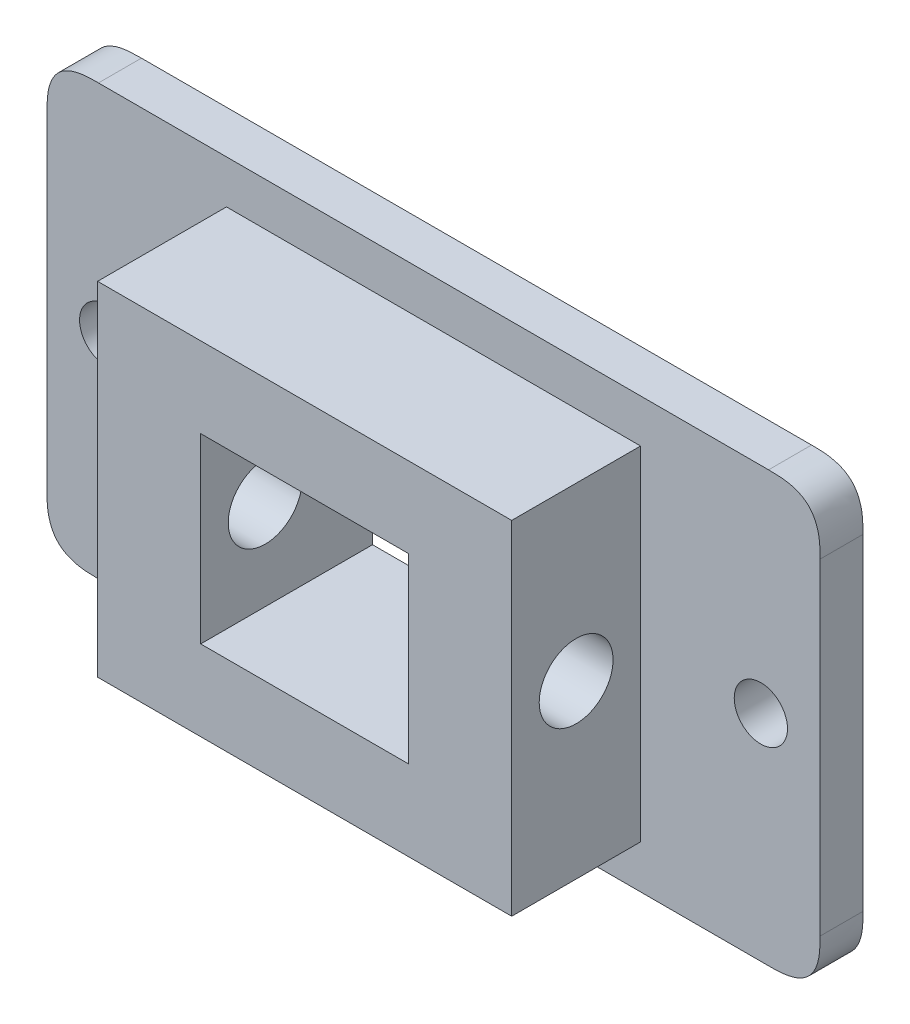
SolidWorks part; units mm, degrees
ref_plane "Front Plane" through (0, 0, 0) normal (0, 0, 1) x (1, 0, 0)
ref_plane "Top Plane" through (0, 0, 0) normal (0, 1, 0) x (1, 0, 0)
ref_plane "Right Plane" through (0, 0, 0) normal (1, 0, 0) x (0, 0, -1)
sketch "Sketch1" plane through (0, 0, 0) normal (0, 0, 1) x (1, 0, 0)
  line L1 (-6.05, 5.3) -> (6.05, 5.3)
  line L2 (-6.05, 5.3) -> (-6.05, -5.3)
  line L3 (-6.05, -5.3) -> (6.05, -5.3)
  line L4 (6.05, 5.3) -> (6.05, -5.3)
  line L5 (-6.05, 5.3) -> (6.05, -5.3) construction
  line L6 (-6.05, -5.3) -> (6.05, 5.3) construction
  line L7 (-22.5, 12.5) -> (22.5, 12.5)
  line L8 (-22.5, 12.5) -> (-22.5, -12.5)
  line L9 (-22.5, -12.5) -> (22.5, -12.5)
  line L10 (22.5, 12.5) -> (22.5, -12.5)
  line L11 (-22.5, 12.5) -> (22.5, -12.5) construction
  line L12 (-22.5, -12.5) -> (22.5, 12.5) construction
  point P0 (0, 0)
  point P5 (0, 0)
  dimension "D1" = 10.6
  dimension "D2" = 12.1
  dimension "D3" = 25
  dimension "D4" = 45
extrude "Boss-Extrude1" add sketch "Sketch1" along normal blind 2.5
sketch "Sketch2" plane through (0, 0, 2.5) normal (0, 0, 1) x (1, 0, 0)
  line L1 (-6.05, -5.3) -> (6.05, -5.3)
  line L2 (-6.05, -5.3) -> (-6.05, -12.5)
  line L3 (-6.05, -12.5) -> (6.05, -12.5)
  line L4 (6.05, -5.3) -> (6.05, -12.5)
  line L5 (-22.5, -12.5) -> (22.5, -12.5) construction
  line L6 (22.5, 12.5) -> (-22.5, 12.5) construction
  line L7 (6.05, 5.3) -> (-6.05, 5.3)
  line L8 (6.05, 5.3) -> (6.05, 12.5)
  line L9 (6.05, 12.5) -> (-6.05, 12.5)
  line L10 (-6.05, 5.3) -> (-6.05, 12.5)
  dimension "D1" = 7.2
  dimension "D2" = 12.1
  dimension "D3" = 12.1
extrude "Boss-Extrude2" add sketch "Sketch2" along normal blind 7.5
sketch "Sketch3" plane through (0, 0, 0) normal (1, 0, 0) x (0, 0, -1)
  line L0 (0, -5.3) -> (-10, -5.3) construction
  line L1 (-10, -5.3) -> (-2.5, -5.3) construction
  line L2 (-10, -5.3) -> (-10, 5.3) construction
  line L3 (-2.5, -5.3) -> (-10, -5.3) construction
  line L4 (-2.5, -12.5) -> (-2.5, 12.5) construction
  line L6 (-2.5, 12.5) -> (-10, 12.5)
  line L7 (-2.5, 12.5) -> (-2.5, -12.5)
  line L8 (-2.5, -12.5) -> (-10, -12.5)
  line L9 (-10, 12.5) -> (-10, -12.5)
  circle A0 centre (-6.25, 0) radius 2.15
  point P12 (-6.25, -5.3)
  dimension "D3" = 4.3
  dimension "D1" = 10
  dimension "D2" = 10.6
extrude "Boss-Extrude3" add sketch "Sketch3" along normal blind 6 from surface starting at face at (6.05, -8.9, 6.25)
extrude "Boss-Extrude4" add sketch "Sketch3<2>" against normal blind 8 from surface starting at face at (-6.05, -8.9, 6.25)
sketch "Sketch3<2>" plane through (0, 0, 0) normal (1, 0, 0) x (0, 0, -1) same geometry as "Sketch3"
sketch "Sketch5" plane through (0, 0, 0) normal (0, 0, -1) x (-1, 0, 0)
  line L0 (-22.5, -12.5) -> (-22.5, 12.5) construction
  line L1 (22.5, 12.5) -> (22.5, -12.5) construction
  line L2 (14.05, -12.5) -> (14.05, 12.5) construction
  line L3 (-12.05, -12.5) -> (-12.05, 12.5) construction
  line L4 (-22.5, -12.5) -> (-22.5, 12.5) construction
  line L5 (22.5, 12.5) -> (22.5, -12.5) construction
  line L6 (14.05, -12.5) -> (14.05, 12.5) construction
  line L7 (-12.05, -12.5) -> (-12.05, 12.5) construction
  line L8 (-22.5, 0) -> (-12.05, 0) construction
  line L9 (0, 8.9015) -> (0, -15.5997) construction
  circle A0 centre (-19.05, 0) radius 1.55
  circle A1 centre (19.05, 0) radius 1.55
  dimension "D1" = 3.1
  dimension "D2" = 7
extrude "Cut-Extrude1" cut sketch "Sketch5" against normal blind 10
fillet "Fillet1" radius 3 4 edges at (-22.5, -12.5, 1.25) (22.5, -12.5, 1.25) (-22.5, 12.5, 1.25) (22.5, 12.5, 1.25) curvature continuous yes
sketch "Sketch6" plane through (0, 0, 10) normal (0, 0, 1) x (1, 0, 0)
  line L1 (-12.05, 9.9769) -> (12.05, 9.9769)
  line L2 (-12.05, 9.9769) -> (-12.05, -9.9769)
  line L3 (-12.05, -9.9769) -> (12.05, -9.9769)
  line L4 (12.05, 9.9769) -> (12.05, -9.9769)
  line L5 (-12.05, 9.9769) -> (12.05, -9.9769) construction
  line L6 (-12.05, -9.9769) -> (12.05, 9.9769) construction
  line L7 (12.05, 12.5) -> (12.05, -12.5) construction
  point P0 (0, 0)
  dimension "D1" = 19.9538
  dimension "D2" = 24.1
extrude "Cut-Extrude2" cut sketch "Sketch6" against normal up to surface (7.5 mm away) flip side to cut up to face at (20.6, 0, 2.5)
sketch "Sketch7" plane through (0, 0, 0) normal (0, 0, -1) x (-1, 0, 0)
  circle A0 centre (-19.05, 0) radius 1.55 construction
  circle A1 centre (-19.05, 0) radius 1.55
